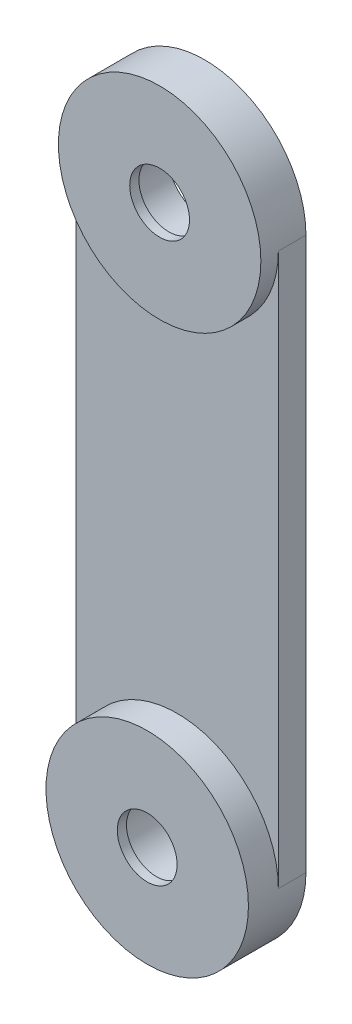
SolidWorks part; units mm, degrees
ref_plane "Plano frontal" through (0, 0, 0) normal (0, 0, 1) x (1, 0, 0)
ref_plane "Plano superior" through (0, 0, 0) normal (0, 1, 0) x (1, 0, 0)
ref_plane "Plano direito" through (0, 0, 0) normal (1, 0, 0) x (0, 0, -1)
sketch "Esboço1" plane through (0, 0, 0) normal (0, 0, 1) x (1, 0, 0)
  circle A3 centre (13.3842, -8.4275) radius 11 construction
  circle A5 centre (13.3842, -8.4275) radius 11
extrude "Ressalto-extrusão1" add sketch "Esboço1" against normal offset from surface (1.9 mm away) 2 offset beyond the face yes
sketch "Esboço3" plane through (0, 0, -1.9) normal (0, 0, -1) x (-1, 0, 0)
  line L0 (-24.3842, -8.4275) -> (-24.3842, -68.4275)
  line L1 (-2.3842, -8.4275) -> (-2.3842, -68.4275)
  arc A0 (-24.3842, -68.4275) -> (-2.3842, -68.4275) centre (-13.3842, -68.4275) ccw
  arc A7 (-2.3842, -8.4275) -> (-24.3842, -8.4275) centre (-13.3842, -8.4275) ccw
  circle A8 centre (-13.3842, -8.4275) radius 11 construction
  dimension "D1" = 60
extrude "Ressalto-extrusão3" add sketch "Esboço3" along normal blind 3
sketch "Esboço4" plane through (0, 0, -4.9) normal (0, 0, -1) x (-1, 0, 0)
  circle A0 centre (-13.3842, -8.4275) radius 3.25 construction
  circle A1 centre (-13.3842, -8.4275) radius 3.25
extrude "Corte-extrusão2" cut sketch "Esboço4" against normal through all
sketch "Esboço5" plane through (0, 0, -4.9) normal (0, 0, -1) x (-1, 0, 0)
  circle A0 centre (-13.3842, -8.4275) radius 4 construction
  circle A1 centre (-13.3842, -8.4275) radius 4
extrude "Corte-extrusão5" cut sketch "Esboço5" against normal offset from surface (3.9 mm away) 1 up to face at (10.1342, -8.4275, 0)
sketch "Esboço6" plane through (0, 0, -1.9) normal (0, 0, 1) x (1, 0, 0)
  circle A0 centre (13.3842, -68.4275) radius 11
  arc A1 (2.3842, -68.4275) -> (24.3842, -68.4275) centre (13.3842, -68.4275) ccw construction
extrude "Ressalto-extrusão4" add sketch "Esboço6" along normal offset from surface (3.25 mm away) 1 offset beyond the face yes
sketch "Esboço7" plane through (0, 0, -4.9) normal (0, 0, -1) x (-1, 0, 0)
  circle A0 centre (-13.3842, -68.4275) radius 4 construction
  circle A1 centre (-13.3842, -68.4275) radius 4
extrude "Corte-extrusão6" cut sketch "Esboço7" against normal offset from surface (5.25 mm away) 1 up to face at (13.3842, -79.4275, 1.35)
sketch "Esboço8" plane through (0, 0, -4.9) normal (0, 0, -1) x (-1, 0, 0)
  circle A0 centre (-13.3842, -68.4275) radius 3.25 construction
  circle A1 centre (-13.3842, -68.4275) radius 3.25
extrude "Corte-extrusão7" cut sketch "Esboço8" against normal through all
